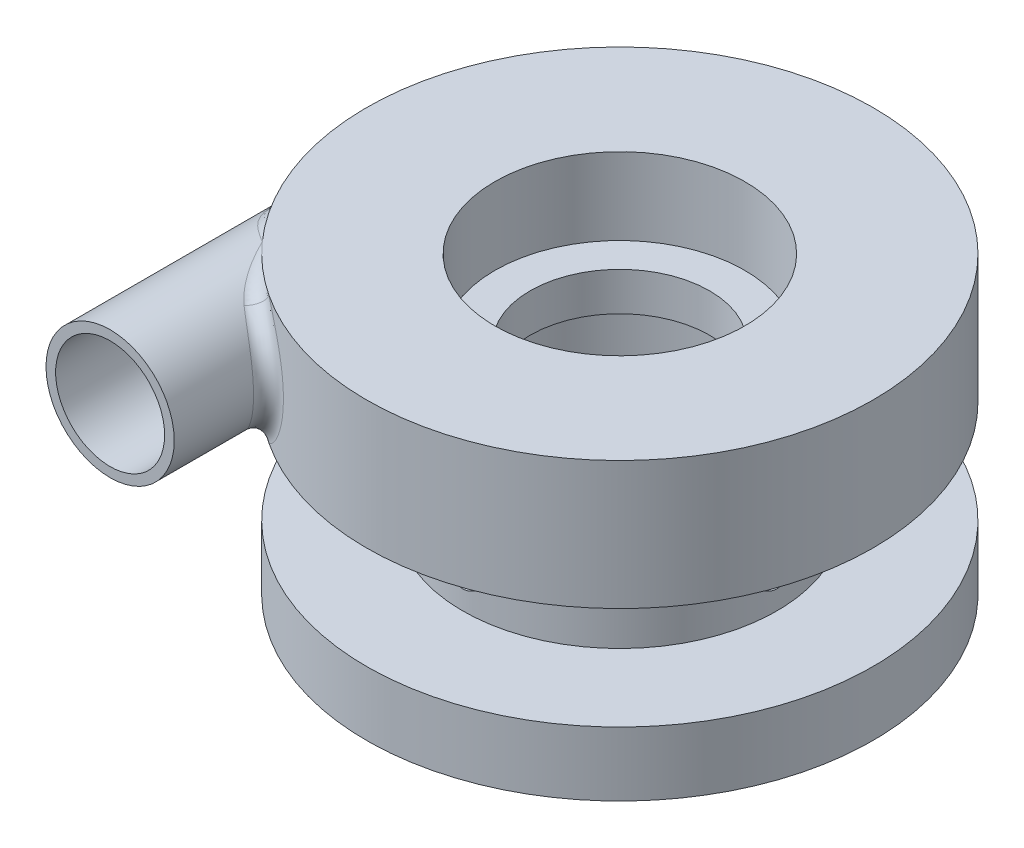
SolidWorks part; units mm, degrees
ref_plane "Front Plane" through (0, 0, 0) normal (0, 0, 1) x (1, 0, 0)
ref_plane "Top Plane" through (0, 0, 0) normal (0, 1, 0) x (1, 0, 0)
ref_plane "Right Plane" through (0, 0, 0) normal (1, 0, 0) x (0, 0, -1)
sketch "Sketch2" plane through (0, 0, 0) normal (0, 0, 1) x (1, 0, 0)
  line L0 (0, 87.5455) -> (0, -67.9094) construction
  line L1 (3.25, 0) -> (9.75, 0)
  line L2 (9.75, 0) -> (9.75, 2)
  line L3 (9.75, 2) -> (19.75, 2)
  line L4 (19.75, 2) -> (19.75, 7)
  line L5 (19.75, 7) -> (12.25, 7)
  line L6 (12.25, 7) -> (12.25, 15)
  line L7 (12.25, 15) -> (19.75, 15)
  line L8 (19.75, 15) -> (19.75, 25)
  line L9 (19.75, 25) -> (9.75, 25)
  line L10 (9.75, 25) -> (9.75, 19)
  line L11 (10.55, 7) -> (3.25, 7)
  line L12 (3.25, 7) -> (3.25, 0)
  line L13 (9.75, 19) -> (7, 19)
  line L14 (7, 19) -> (7, 16)
  line L15 (7, 16) -> (10.55, 16)
  line L16 (10.55, 16) -> (10.55, 7)
  dimension "D1" = 3.25
  dimension "D2" = 10.55
  dimension "D3" = 9.2
  dimension "D4" = 7.5
  dimension "D5" = 7.5
  dimension "D6" = 5
  dimension "D7" = 2
  dimension "D8" = 8
  dimension "D9" = 10
  dimension "D10" = 7
  dimension "D11" = 7
  dimension "D12" = 6
  dimension "D13" = 3
  dimension "D14" = 9.75
revolve "Revolve1" add sketch "Sketch2" angle 360 about L0
sketch "Sketch3" plane through (0, 0, 0) normal (1, 0, 0) x (0, 0, -1)
  line L0 (0, 25) -> (0, 2) construction
  line L1 (9.75, 25) -> (-9.75, 25) construction
  line L2 (-9.75, 2) -> (9.75, 2) construction
  line L3 (19.75, 7) -> (-19.75, 7) construction
  circle A0 centre (0, 9) radius 0.5
  circle A1 centre (0, 14) radius 0.5
  circle A2 centre (0, 10) radius 1.5
  dimension "D1" = 1
  dimension "D2" = 1
  dimension "D5" = 3
  dimension "D3" = 2
  dimension "D4" = 5
  dimension "D6" = 3
extrude "Cut-Extrude1" cut sketch "Sketch3" against normal through all both and the other way through all contours A2 L0 A0 | L0 A2 A0 | L0 A0 | A0 L0 | L0 A1 | A1 L0 region at (0, 14, -0.2122) region at (0, 10.125, -0.6897) region at (0, 10.125, 0.6897) region at (0, 14, 0.2122) region at (0, 9, -0.2122) region at (0, 9, 0.2122)
pattern_circular "CirPattern1" count 2 every 90 about axis through (0, 25, 0) along (0, 1, 0) of "Cut-Extrude1"
sketch "Sketch5" plane through (0, 0, 0) normal (0, 0, 1) x (1, 0, 0)
  line L0 (-12.25, 15) -> (12.25, 15) construction
  line L1 (-19.75, 25) -> (-19.75, 15) construction
  circle A0 centre (-14.75, 20) radius 4.25
  circle A1 centre (-14.75, 20) radius 5
  dimension "D1" = 8.5
  dimension "D3" = 10
  dimension "D2" = 5
extrude "Cut-Extrude3" cut sketch "Sketch5" along normal blind 38 contours A0 region at (-14.75, 20, 0)
extrude "Boss-Extrude1" add sketch "Sketch5<4>" along normal blind 25
sketch "Sketch5<4>" plane through (0, 0, 0) normal (0, 0, 1) x (1, 0, 0) same geometry as "Sketch5"
fillet "Fillet3" radius 1 3 edges at (-10.3068, 22.293, 16.8473) (-9.7809, 19.4453, 17.158) (-18.3181, 23.5027, 7.3831)
